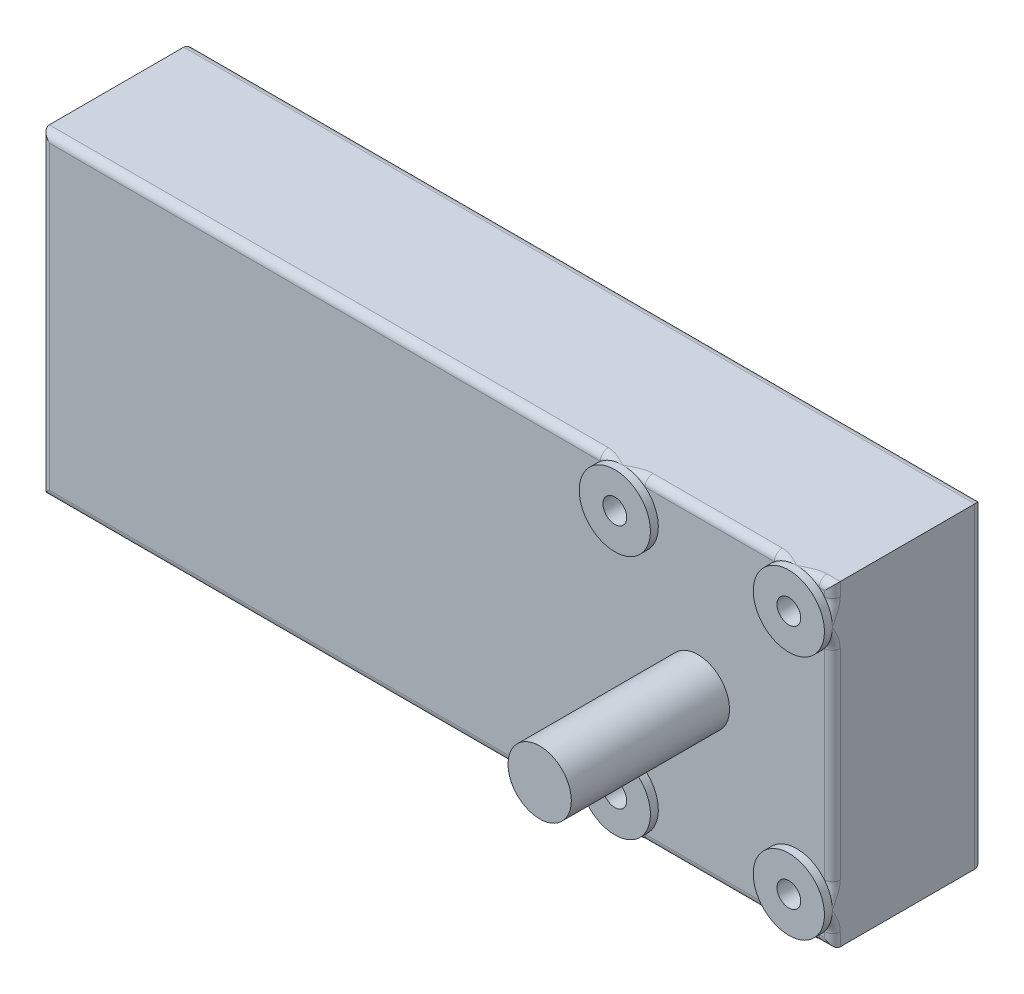
SolidWorks part; units mm, degrees
ref_plane "Alzado" through (0, 0, 0) normal (0, 0, 1) x (1, 0, 0)
ref_plane "Planta" through (0, 0, 0) normal (0, 1, 0) x (1, 0, 0)
ref_plane "Vista lateral" through (0, 0, 0) normal (1, 0, 0) x (0, 0, -1)
sketch "Croquis1" plane through (0, 0, 0) normal (0, 0, 1) x (1, 0, 0)
  line L1 (-50, -20) -> (50, -20)
  line L2 (-50, -20) -> (-50, 20)
  line L3 (-50, 20) -> (50, 20)
  line L4 (50, -20) -> (50, 20)
  line L5 (-50, -20) -> (50, 20) construction
  line L6 (-50, 20) -> (50, -20) construction
  point P0 (0, 0)
  dimension "D1" = 100
  dimension "D2" = 40
extrude "Saliente-Extruir1" add sketch "Croquis1" along normal blind 19
sketch "Croquis2" plane through (0, 0, 19) normal (0, 0, 1) x (1, 0, 0)
  line L0 (50, -20) -> (50, 20) construction
  line L1 (50, 20) -> (-50, 20) construction
  line L2 (-50, -20) -> (50, -20) construction
  line L4 (45.5, 15.5) -> (23.5, 15.5) construction
  line L5 (45.5, 15.5) -> (45.5, -15.5) construction
  line L6 (45.5, -15.5) -> (23.5, -15.5) construction
  line L7 (23.5, 15.5) -> (23.5, -15.5) construction
  circle A0 centre (45.5, 15.5) radius 4.5
  circle A1 centre (45.5, -15.5) radius 4.5
  circle A2 centre (23.5, -15.5) radius 4.5
  circle A3 centre (23.5, 15.5) radius 4.5
  dimension "D1" = 22
extrude "Saliente-Extruir2" add sketch "Croquis2" along normal blind 1
fillet "Redondeo3" radius 1 14 edges at (50, 0, 0) (0, 20, 0) (0, -20, 0) (-50, 0, 0) (-50, 0, 19) (-13.25, -20, 19) (34.5, -20, 19) (47.75, -20, 19) (50, -17.75, 19) (-13.25, 20, 19) (34.5, 20, 19) (50, 0, 19) (47.75, 20, 19) (50, 17.75, 19)
sketch "Croquis3" plane through (0, 0, 20) normal (0, 0, 1) x (1, 0, 0)
  circle A0 centre (23.5, 15.5) radius 1.5
  circle A1 centre (45.5, 15.5) radius 1.5
  circle A2 centre (45.5, -15.5) radius 1.5
  circle A3 centre (23.5, -15.5) radius 1.5
extrude "Cortar-Extruir1" cut sketch "Croquis3" against normal blind 10
sketch "Croquis4" plane through (0, 0, 19) normal (0, 0, 1) x (1, 0, 0)
  line L1 (50, 15.5) -> (33, 15.5) construction
  line L2 (33, 15.5) -> (33, -15.5) construction
  line L3 (33, -15.5) -> (50, -15.5) construction
  line L4 (50, -15.5) -> (50, 15.5) construction
  circle A2 centre (33, 0) radius 4
  dimension "D1" = 17
extrude "Saliente-Extruir3" add sketch "Croquis4" along normal blind 20
